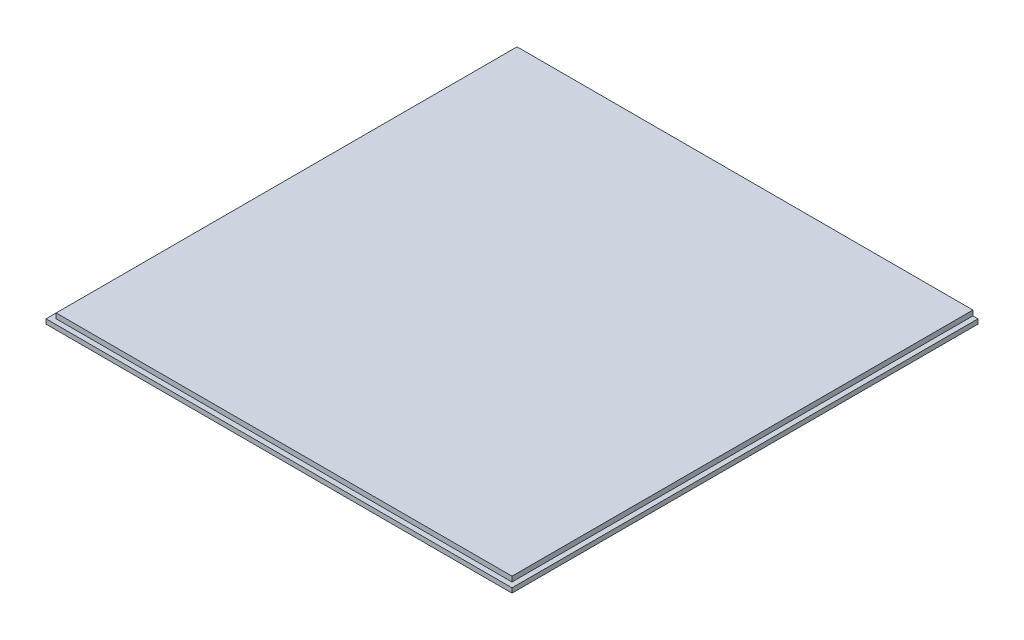
SolidWorks part; units mm, degrees
ref_plane "Front Plane" through (0, 0, 0) normal (0, 0, 1) x (1, 0, 0)
ref_plane "Top Plane" through (0, 0, 0) normal (0, 1, 0) x (1, 0, 0)
ref_plane "Right Plane" through (0, 0, 0) normal (1, 0, 0) x (0, 0, -1)
sketch "Sketch1" plane through (0, 0, 0) normal (0, 1, 0) x (1, 0, 0)
  line L1 (-438.9437, -438.9437) -> (438.9438, -438.9437)
  line L2 (-438.9437, -438.9437) -> (-438.9437, 438.9438)
  line L3 (-438.9437, 438.9438) -> (438.9438, 438.9438)
  line L4 (438.9438, -438.9437) -> (438.9438, 438.9438)
  line L5 (-438.9437, -438.9437) -> (438.9438, 438.9438) construction
  line L6 (-438.9437, 438.9438) -> (438.9438, -438.9437) construction
  point P0 (0, 0)
  dimension "D1" = 877.8875
  dimension "D2" = 877.8875
extrude "Boss-Extrude1" add sketch "Sketch1" along normal blind 18.2562
sketch "Sketch3" plane through (0, 18.2562, 0) normal (0, 1, 0) x (1, 0, 0)
  line L3 (429.4188, 438.9438) -> (438.9437, 438.9437)
  line L5 (438.9437, 438.9437) -> (438.9437, -438.9437)
  line L6 (429.4188, -429.4187) -> (429.4188, 438.9438)
  line L7 (-429.4187, -429.4187) -> (429.4188, -429.4187)
  line L8 (-429.4187, 438.9438) -> (-429.4187, -429.4187)
  line L9 (429.4188, -429.4187) -> (429.4188, 438.9438)
  line L10 (-429.4187, -429.4187) -> (429.4188, -429.4187)
  line L11 (-429.4187, 438.9438) -> (-429.4187, -429.4187)
  line L12 (438.9437, -438.9437) -> (-438.9437, -438.9437)
  line L13 (-438.9437, 438.9437) -> (-438.9437, -438.9437)
  line L14 (438.9437, 438.9437) -> (-438.9437, -438.9437) construction
  line L15 (438.9437, -438.9437) -> (-438.9437, 438.9437) construction
  line L16 (-429.4187, 438.9438) -> (-438.9437, 438.9437)
  point P0 (0, 0)
  dimension "D1" = 9.525
extrude "Cut-Extrude1" cut sketch "Sketch3" against normal blind 9.525
